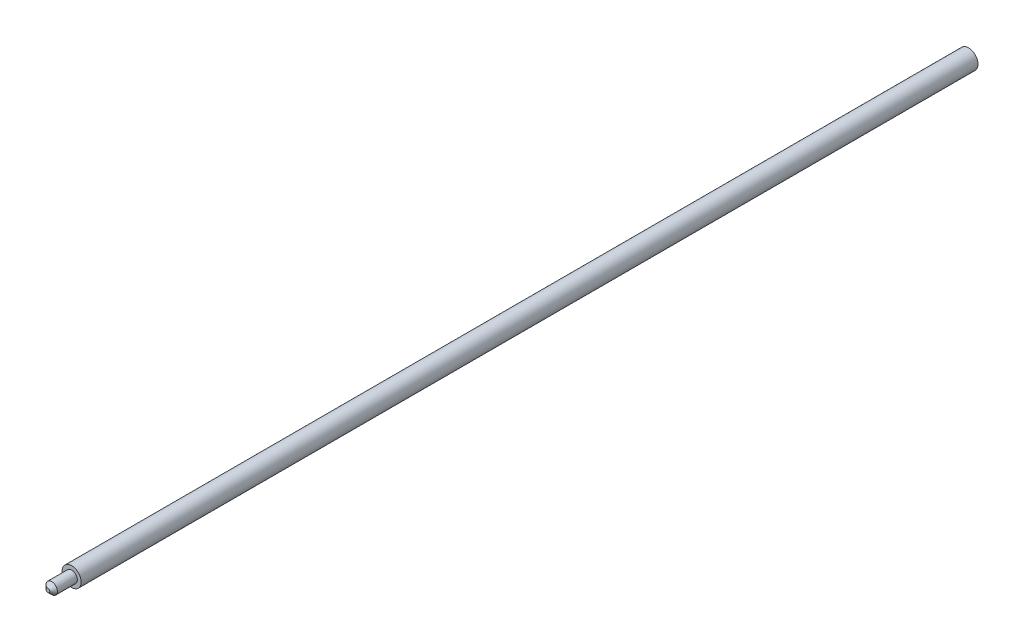
SolidWorks part; units mm, degrees
material "ABS PC"
ref_plane "Front Plane" through (0, 0, 0) normal (0, 0, 1) x (1, 0, 0)
ref_plane "Top Plane" through (0, 0, 0) normal (0, 1, 0) x (1, 0, 0)
ref_plane "Right Plane" through (0, 0, 0) normal (1, 0, 0) x (0, 0, -1)
sketch "Sketch1" plane through (0, 0, 0) normal (0, 0, 1) x (1, 0, 0)
  circle A0 centre (0, 0) radius 1.27
  dimension "D1" = 2.54
extrude "Boss-Extrude1" add sketch "Sketch1" along normal blind 119.9642
sketch "Sketch3" plane through (0, 0, 119.9642) normal (0, 0, 1) x (1, 0, 0)
  circle A0 centre (0, 0) radius 0.762
  dimension "D1" = 1.524
extrude "Boss-Extrude2" add sketch "Sketch3" along normal blind 3.175
ref_axis "Axis1" through (0, 0, -5.334) along (0, 0, 1)
chamfer "Chamfer1" distance 0.508 angle 45 1 edges at (0.762, 0, 123.1392)
